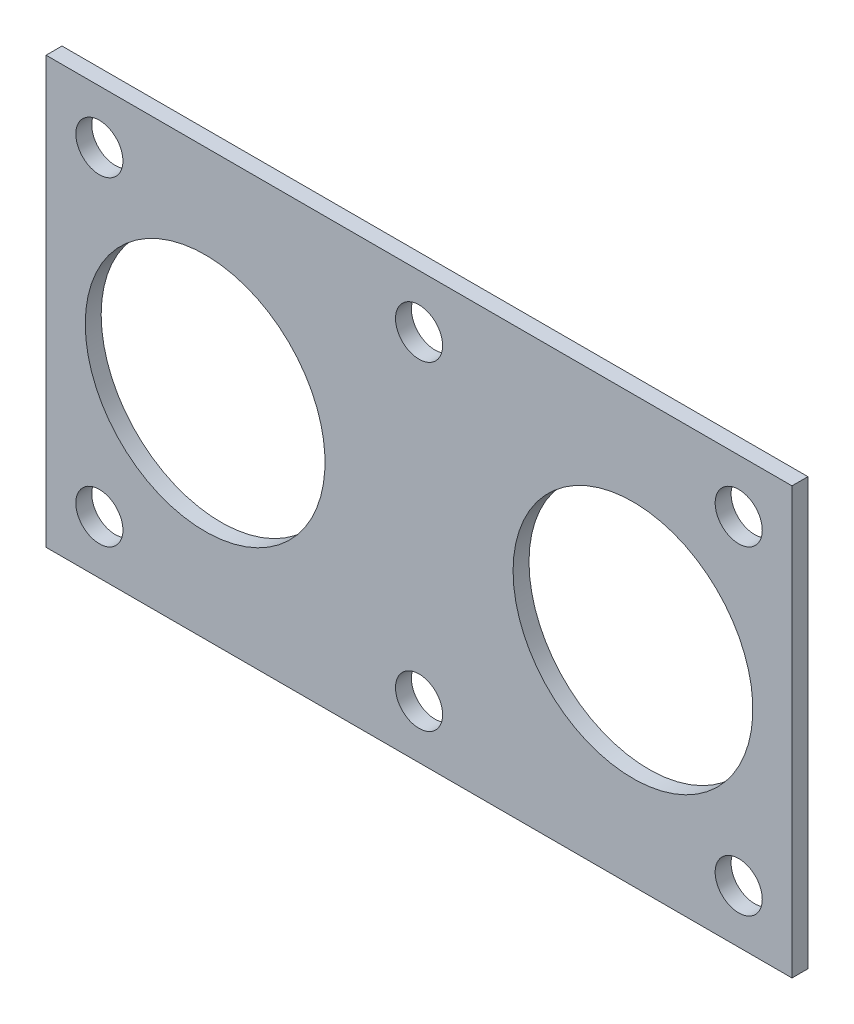
SolidWorks part; units mm, degrees
material "Plain Carbon Steel"
ref_plane "Front Plane" through (0, 0, 0) normal (0, 0, 1) x (1, 0, 0)
ref_plane "Top Plane" through (0, 0, 0) normal (0, 1, 0) x (1, 0, 0)
ref_plane "Right Plane" through (0, 0, 0) normal (1, 0, 0) x (0, 0, -1)
sketch "Sketch1" plane through (0, 0, 0) normal (0, 0, 1) x (1, 0, 0)
  line L0 (-18.9548, 0) -> (69.9452, 0) construction
  line L1 (-18.9548, 25.4) -> (69.9452, 25.4)
  line L2 (-18.9548, 25.4) -> (-18.9547, -25.4)
  line L3 (-18.9547, -25.4) -> (69.9452, -25.4)
  line L4 (69.9452, 25.4) -> (69.9452, -25.4)
  line L5 (25.4953, 25.4) -> (25.4953, -25.4) construction
  circle A2 centre (0, 0) radius 14.2875
  circle A3 centre (50.9905, 0) radius 14.2875
  circle A4 centre (0, 0) radius 14.2875 construction
  circle A5 centre (50.9905, 0) radius 14.2875 construction
  dimension "D1" = 50.8
  dimension "D2" = 88.9
extrude "Boss-Extrude1" add sketch "Sketch1" along normal blind 1.8974
hole_wizard "#10 Clearance Hole1" positions "Sketch2" profile "Sketch3" hole size "#10" standard "ANSI Inch" end condition through all
sketch "Sketch2" plane through (-41.275, -44.45, 1.8974) normal (0, 0, 1) x (1, 0, 0)
  line L16 (28.6702, 63.5) -> (28.6702, 25.4)
  line L17 (28.6702, 25.4) -> (104.8702, 25.4)
  line L18 (104.8702, 25.4) -> (104.8702, 63.5)
  line L19 (104.8702, 63.5) -> (28.6702, 63.5)
  point P0 (104.8702, 63.5)
  point P2 (28.6702, 63.5)
  point P4 (66.7702, 25.4)
  point P6 (28.6702, 25.4)
  point P8 (66.7702, 63.5)
  point P10 (104.8702, 25.4)
  point P22 (0, 0)
  point P51 (24.8602, 67.31)
  point P52 (66.7702, 67.31)
  point P53 (108.6802, 67.31)
  point P54 (108.6802, 21.59)
  point P55 (66.7702, 21.59)
  point P56 (24.8602, 21.59)
sketch "Sketch3" plane through (63.5952, 19.05, 1.8974) normal (1, 0, 0) x (0, -1, 0)
  line L0 (0, 0) -> (0, 1.8974)
  line L1 (0, 1.8974) -> (2.8067, 1.8974)
  line L2 (2.8067, 1.8974) -> (2.8067, 0)
  line L3 (2.8067, 0) -> (0, 0)
  line L4 (0, -6.35) -> (0, 107.95) construction
  dimension "Thru Hole Dia." = 5.6134
  dimension "Thru Hole Depth" = 1.8974
